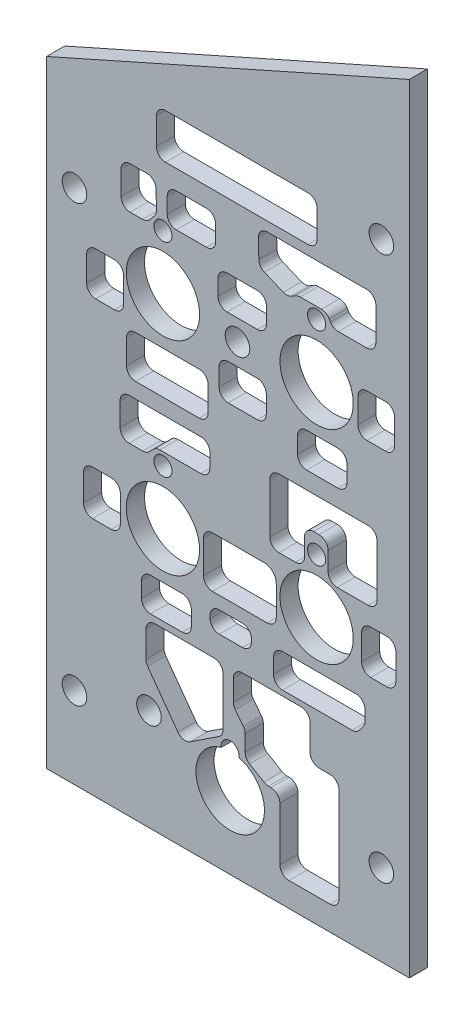
SolidWorks part; units mm, degrees
material "PET"
ref_plane "Front Plane" through (0, 0, 0) normal (0, 0, 1) x (1, 0, 0)
ref_plane "Top Plane" through (0, 0, 0) normal (0, 1, 0) x (1, 0, 0)
ref_plane "Right Plane" through (0, 0, 0) normal (1, 0, 0) x (0, 0, -1)
sketch "Sketch1" plane through (0, 0, 0) normal (0, 0, 1) x (1, 0, 0)
  line L4 (0, 107.95) -> (0, 0)
  line L5 (0, 0) -> (63.5, 0)
  line L6 (63.5, 0) -> (63.5, 136.2202)
  line L7 (63.5, 136.2202) -> (0, 107.95)
  line L8 (0, 107.95) -> (0, 0)
  line L9 (0, 0) -> (63.5, 0)
  line L10 (63.5, 0) -> (63.5, 136.2202)
  line L11 (63.5, 136.2202) -> (0, 107.95)
  dimension "D1" = 0
extrude "Boss-Extrude1" add sketch "Sketch1" against normal blind 3.175
hole_wizard "#6 Clearance Hole1" positions "Sketch4" profile "Sketch3" hole size "#6" standard "ANSI Inch" end condition through all
sketch "Sketch4" plane through (0, 0, 0) normal (0, 0, 1) x (1, 0, 0)
  point P0 (58.6105, 14.2875)
  point P3 (4.8895, 14.2875)
  point P6 (4.8895, 90.4875)
  point P9 (58.6105, 109.5375)
sketch "Sketch3" plane through (58.6105, 14.2875, 0) normal (1, 0, 0) x (0, -1, 0)
  line L0 (0, 0) -> (0, 3.175)
  line L1 (0, 3.175) -> (2.1526, 3.175)
  line L2 (2.1526, 3.175) -> (2.1526, 0)
  line L5 (2.1526, 0) -> (0, 0)
  line L11 (0, -6.35) -> (0, 107.95) construction
  dimension "Thru Hole Dia." = 4.3053
  dimension "Thru Hole Depth" = 3.175
sketch "Sketch8" plane through (0, 0, 0) normal (0, 0, 1) x (1, 0, 0)
  line L0 (0, 0) -> (63.5, 0) construction
  line L1 (20.3732, 91.7104) -> (20.3732, 82.1854) construction
  line L2 (20.3732, 56.073) -> (20.3732, 46.548) construction
  line L3 (47.2705, 46.548) -> (47.2705, 56.073) construction
  line L4 (32.1439, 18.7) -> (32.1439, 12.7) construction
  line L5 (81.6444, 34.0155) -> (81.6444, 24.4905) construction
  line L6 (47.2705, 82.1854) -> (47.2705, 91.7104) construction
  line L7 (0, 107.95) -> (0, 0) construction
  circle A1 centre (20.3732, 91.7104) radius 1.5875
  circle A2 centre (47.2705, 91.7104) radius 1.5875
  circle A3 centre (47.2705, 56.073) radius 1.5875
  circle A4 centre (32.1439, 12.7) radius 3.75
  circle A5 centre (20.3732, 56.073) radius 1.5875
  circle A6 centre (32.1439, 18.7) radius 1.5875
  circle A10 centre (47.2705, 46.548) radius 6.4135
  circle A12 centre (47.2705, 82.1854) radius 6.4135
  circle A15 centre (20.3732, 82.1854) radius 6.4135
  circle A17 centre (20.3732, 46.548) radius 6.4135
  circle A18 centre (81.6444, 34.0155) radius 1.651 construction
  circle A19 centre (81.6444, 24.4905) radius 6.4135 construction
  dimension "D2" = 26.8973
  dimension "D3" = 12.827
  dimension "D9" = 3.175
  dimension "D10" = 3.175
  dimension "D11" = 3.175
  dimension "D12" = 3.175
  dimension "D13" = 3.175
  dimension "D14" = 7.5
  dimension "D1" = 9.525
  dimension "D4" = 35.6374
  dimension "D5" = 33.848
  dimension "D6" = 15.1266
  dimension "D7" = 12.7
  dimension "D8" = 32.1439
  dimension "D15" = 6
extrude "Cut-Extrude1" cut sketch "Sketch8" against normal through all
hole_wizard "#6 Clearance Hole2" positions "Sketch9" profile "Sketch10" hole size "#6" standard "ANSI Inch" end condition through all
sketch "Sketch9" plane through (31.75, 0, 4.765) normal (0, 0, 1) x (1, 0, 0)
  point P0 (1.6763, 81.3834)
  point P2 (-13.8187, 17.7712)
sketch "Sketch10" plane through (33.4263, 81.3834, 4.765) normal (1, 0, 0) x (0, -1, 0)
  line L0 (0, 0) -> (0, 7.94)
  line L1 (0, 7.94) -> (2.1526, 7.94)
  line L2 (2.1526, 7.94) -> (2.1526, 0)
  line L3 (2.1526, 0) -> (0, 0)
  line L4 (0, -6.35) -> (0, 107.95) construction
  dimension "Thru Hole Dia." = 4.3053
  dimension "Thru Hole Depth" = 7.94
sketch "Sketch11" plane through (0, 0, 0) normal (0, 0, 1) x (1, 0, 0)
  line L36 (45.5237, 74.0554) -> (50.9898, 74.0554)
  line L37 (43.9362, 72.4679) -> (43.9362, 69.6013)
  line L38 (45.5237, 68.0138) -> (50.9898, 68.0138)
  line L39 (52.5773, 72.4679) -> (52.5773, 69.6013)
  line L41 (13.9834, 72.3188) -> (13.9834, 68.071)
  line L47 (28.2901, 72.3188) -> (28.2901, 68.071)
  line L120 (56.0781, 85.2958) -> (59.3407, 85.2958)
  line L121 (54.4906, 83.7083) -> (54.4906, 79.3729)
  line L122 (56.0781, 77.7854) -> (59.3407, 77.7854)
  line L123 (60.9282, 83.7083) -> (60.9282, 79.3729)
  line L124 (8.6064, 83.088) -> (11.8928, 83.088)
  line L125 (7.0189, 81.5005) -> (7.0189, 77.085)
  line L126 (8.6064, 75.4975) -> (11.8928, 75.4975)
  line L127 (13.4803, 81.5005) -> (13.4803, 77.085)
  line L132 (31.7883, 77.6009) -> (36.873, 77.6009)
  line L133 (30.2008, 76.0134) -> (30.2008, 72.9194)
  line L134 (31.7883, 71.3319) -> (36.873, 71.3319)
  line L135 (38.4605, 76.0134) -> (38.4605, 72.9194)
  line L140 (20.8125, 110.1622) -> (45.7836, 110.1622)
  line L141 (47.3711, 108.5747) -> (47.3711, 103.9202)
  line L142 (45.7836, 102.3327) -> (20.8125, 102.3327)
  line L143 (19.225, 103.9202) -> (19.225, 108.5747)
  line L144 (57.6403, 99.0765) -> (57.6403, 93.3678)
  line L145 (56.0528, 91.7803) -> (51.0669, 91.7803)
  line L146 (49.7101, 92.5437) -> (49.4755, 92.93)
  line L147 (48.1187, 93.6933) -> (44.3958, 93.6933)
  line L148 (43.5716, 93.4626) -> (42.8862, 93.0463)
  line L149 (41.4551, 92.9362) -> (38.1407, 94.3076)
  line L150 (37.1609, 95.7286) -> (37.0654, 99.0307)
  line L151 (38.6523, 100.664) -> (56.0528, 100.664)
  line L152 (13.0431, 97.4222) -> (13.0431, 93.2456)
  line L153 (14.6306, 91.6581) -> (16.8223, 91.6581)
  line L154 (18.0448, 92.2329) -> (18.8858, 93.2482)
  line L155 (19.2501, 94.3076) -> (19.1571, 97.4689)
  line L156 (17.5703, 99.0097) -> (14.6306, 99.0097)
  line L157 (21.1275, 97.349) -> (21.1275, 94.6082)
  line L158 (22.715, 93.0207) -> (28.002, 93.0207)
  line L159 (29.5895, 94.6082) -> (29.5895, 97.349)
  line L160 (28.002, 98.9365) -> (22.715, 98.9365)
  line L161 (30.0099, 89.3456) -> (30.0099, 86.6058)
  line L162 (31.5974, 85.0183) -> (36.9051, 85.0183)
  line L163 (38.4926, 86.6058) -> (38.4926, 89.3456)
  line L164 (36.9051, 90.9331) -> (31.5974, 90.9331)
  line L165 (15.5709, 73.9063) -> (26.7026, 73.9063)
  line L166 (15.5709, 66.4835) -> (26.7026, 66.4835)
  line L167 (39.0901, 54.653) -> (39.0901, 63.4087)
  line L168 (40.6776, 64.9962) -> (56.2883, 64.9962)
  line L169 (57.8758, 63.4087) -> (57.8758, 54.4828)
  line L170 (56.2883, 52.8953) -> (50.8752, 52.8953)
  line L171 (49.2877, 54.4828) -> (49.2877, 57.7132)
  line L172 (47.7002, 59.3007) -> (46.7435, 59.3007)
  line L173 (45.156, 57.7132) -> (45.156, 54.653)
  line L174 (43.5685, 53.0655) -> (40.6776, 53.0655)
  line L175 (55.758, 36.8172) -> (55.758, 35.0552)
  line L176 (34.2696, 35.4833) -> (30.227, 35.4833)
  line L177 (35.8571, 37.0708) -> (35.8571, 37.5884)
  line L178 (34.2696, 39.1759) -> (30.227, 39.1759)
  line L179 (28.6395, 37.0708) -> (28.6395, 37.5884)
  line L180 (55.4332, 34.0931) -> (54.7305, 33.1708)
  line L181 (53.4677, 32.5454) -> (41.3186, 32.5454)
  line L182 (39.7311, 34.1329) -> (39.7311, 36.8172)
  line L183 (41.3186, 38.4047) -> (54.1705, 38.4047)
  line L184 (25.1503, 16.6335) -> (30.1748, 19.9489)
  line L185 (30.8879, 21.2739) -> (30.8879, 29.8393)
  line L186 (29.3004, 31.4268) -> (18.9703, 31.4268)
  line L187 (17.3828, 29.8393) -> (17.3828, 25.2871)
  line L188 (17.6844, 24.3562) -> (22.9901, 17.0276)
  line L189 (32.6889, 30.0523) -> (32.6889, 26.4288)
  line L190 (33.0249, 25.4521) -> (34.4315, 23.6499)
  line L193 (40.8468, 15.1629) -> (40.8468, 5.8443)
  line L194 (42.4343, 4.2568) -> (49.6158, 4.2568)
  line L195 (51.2033, 5.8443) -> (51.2033, 22.3324)
  line L196 (49.6158, 23.9199) -> (47.7144, 23.9199)
  line L197 (46.1269, 25.5074) -> (46.1269, 30.0523)
  line L198 (44.5394, 31.6398) -> (34.2764, 31.6398)
  line L204 (38.1, 50.2578) -> (29.0541, 50.2578)
  line L205 (40.2083, 48.1495) -> (40.2083, 42.9683)
  line L206 (38.6208, 41.3808) -> (29.0541, 41.3808)
  line L207 (27.4666, 48.6703) -> (27.4666, 42.9683)
  line L210 (12.8755, 62.2158) -> (12.8755, 58.1379)
  line L211 (11.3334, 41.9242) -> (8.0566, 41.9242)
  line L212 (12.9209, 43.5117) -> (12.9209, 48.1495)
  line L213 (11.3334, 49.737) -> (8.0566, 49.737)
  line L214 (6.4691, 43.5117) -> (6.4691, 48.1495)
  line L215 (14.463, 56.5504) -> (16.8417, 56.5504)
  line L216 (17.9642, 57.0153) -> (18.708, 57.7591)
  line L217 (19.8305, 58.2241) -> (27.0058, 58.2241)
  line L218 (28.5933, 59.8116) -> (28.5933, 62.2158)
  line L219 (27.0058, 63.8033) -> (14.463, 63.8033)
  line L221 (18.2021, 38.4047) -> (23.7519, 38.4047)
  line L222 (16.6146, 36.8172) -> (16.6146, 34.1329)
  line L223 (18.2021, 32.5454) -> (23.7519, 32.5454)
  line L224 (25.3394, 36.8172) -> (25.3394, 34.1329)
  line L225 (56.7376, 49.8291) -> (59.5564, 49.8291)
  line L226 (55.1501, 48.2416) -> (55.1501, 43.7598)
  line L227 (56.7376, 42.1723) -> (59.5564, 42.1723)
  line L228 (61.1439, 48.2416) -> (61.1439, 43.7598)
  line L230 (34.7676, 22.6732) -> (34.7676, 19.8429)
  line L231 (35.535, 18.4836) -> (38.0298, 16.9786)
  line L232 (38.8498, 16.7504) -> (39.2593, 16.7504)
  circle A0 centre (32.1439, 12.7) radius 6
  arc A1 (20.8125, 102.3327) -> (19.225, 103.9202) centre (20.8125, 103.9202) cw
  arc A2 (47.3711, 103.9202) -> (45.7836, 102.3327) centre (45.7836, 103.9202) cw
  arc A3 (45.7836, 110.1622) -> (47.3711, 108.5747) centre (45.7836, 108.5747) cw
  arc A4 (20.8125, 110.1622) -> (19.225, 108.5747) centre (20.8125, 108.5747) ccw
  arc A9 (36.873, 77.6009) -> (38.4605, 76.0134) centre (36.873, 76.0134) cw
  arc A10 (30.2008, 72.9194) -> (31.7883, 71.3319) centre (31.7883, 72.9194) ccw
  arc A11 (36.873, 71.3319) -> (38.4605, 72.9194) centre (36.873, 72.9194) ccw
  arc A12 (31.7883, 77.6009) -> (30.2008, 76.0134) centre (31.7883, 76.0134) ccw
  arc A13 (11.8928, 83.088) -> (13.4803, 81.5005) centre (11.8928, 81.5005) cw
  arc A14 (7.0189, 77.085) -> (8.6064, 75.4975) centre (8.6064, 77.085) ccw
  arc A15 (11.8928, 75.4975) -> (13.4803, 77.085) centre (11.8928, 77.085) ccw
  arc A16 (8.6064, 83.088) -> (7.0189, 81.5005) centre (8.6064, 81.5005) ccw
  arc A17 (59.3407, 85.2958) -> (60.9282, 83.7083) centre (59.3407, 83.7083) cw
  arc A18 (54.4906, 79.3729) -> (56.0781, 77.7854) centre (56.0781, 79.3729) ccw
  arc A19 (59.3407, 77.7854) -> (60.9282, 79.3729) centre (59.3407, 79.3729) ccw
  arc A20 (56.0781, 85.2958) -> (54.4906, 83.7083) centre (56.0781, 83.7083) ccw
  arc A29 (46.1269, 30.0523) -> (44.5394, 31.6398) centre (44.5394, 30.0523) ccw
  arc A30 (47.7144, 23.9199) -> (46.1269, 25.5074) centre (47.7144, 25.5074) cw
  arc A31 (49.6158, 4.2568) -> (51.2033, 5.8443) centre (49.6158, 5.8443) ccw
  arc A32 (51.2033, 22.3324) -> (49.6158, 23.9199) centre (49.6158, 22.3324) ccw
  arc A33 (40.8468, 5.8443) -> (42.4343, 4.2568) centre (42.4343, 5.8443) ccw
  arc A36 (34.4315, 23.6499) -> (34.7676, 22.6732) centre (33.1801, 22.6732) cw
  arc A37 (32.6889, 26.4288) -> (33.0249, 25.4521) centre (34.2764, 26.4288) ccw
  arc A38 (32.6889, 30.0523) -> (34.2764, 31.6398) centre (34.2764, 30.0523) cw
  arc A39 (17.3828, 25.2871) -> (17.6844, 24.3562) centre (18.9703, 25.2871) ccw
  arc A40 (18.9703, 31.4268) -> (17.3828, 29.8393) centre (18.9703, 29.8393) ccw
  arc A41 (30.8879, 29.8393) -> (29.3004, 31.4268) centre (29.3004, 29.8393) ccw
  arc A42 (29.0541, 50.2578) -> (27.4666, 48.6703) centre (29.0541, 48.6703) ccw
  arc A43 (40.2083, 42.9683) -> (38.6208, 41.3808) centre (38.6208, 42.9683) cw
  arc A44 (29.0541, 41.3808) -> (27.4666, 42.9683) centre (29.0541, 42.9683) cw
  arc A46 (38.1, 50.2578) -> (40.2083, 48.1495) centre (38.1, 48.1495) cw
  arc A49 (26.7026, 73.9063) -> (28.2901, 72.3188) centre (26.7026, 72.3188) cw
  arc A50 (30.1748, 19.9489) -> (30.8879, 21.2739) centre (29.3004, 21.2739) ccw
  arc A51 (26.7026, 66.4835) -> (28.2901, 68.071) centre (26.7026, 68.071) ccw
  arc A52 (25.1503, 16.6335) -> (22.9901, 17.0276) centre (24.276, 17.9585) cw
  arc A53 (39.7311, 36.8172) -> (41.3186, 38.4047) centre (41.3186, 36.8172) cw
  arc A54 (13.9834, 68.071) -> (15.5709, 66.4835) centre (15.5709, 68.071) ccw
  arc A55 (54.7305, 33.1708) -> (53.4677, 32.5454) centre (53.4677, 34.1329) cw
  arc A56 (15.5709, 73.9063) -> (13.9834, 72.3188) centre (15.5709, 72.3188) ccw
  arc A57 (50.9898, 74.0554) -> (52.5773, 72.4679) centre (50.9898, 72.4679) cw
  arc A58 (43.9362, 69.6013) -> (45.5237, 68.0138) centre (45.5237, 69.6013) ccw
  arc A59 (50.9898, 68.0138) -> (52.5773, 69.6013) centre (50.9898, 69.6013) ccw
  arc A60 (45.5237, 74.0554) -> (43.9362, 72.4679) centre (45.5237, 72.4679) ccw
  arc A61 (41.3186, 32.5454) -> (39.7311, 34.1329) centre (41.3186, 34.1329) cw
  arc A62 (55.758, 35.0552) -> (55.4332, 34.0931) centre (54.1705, 35.0552) cw
  arc A63 (55.758, 36.8172) -> (54.1705, 38.4047) centre (54.1705, 36.8172) ccw
  arc A64 (30.227, 35.4833) -> (28.6395, 37.0708) centre (30.227, 37.0708) cw
  arc A65 (35.8571, 37.5884) -> (34.2696, 39.1759) centre (34.2696, 37.5884) ccw
  arc A66 (40.6776, 53.0655) -> (39.0901, 54.653) centre (40.6776, 54.653) cw
  arc A67 (45.156, 54.653) -> (43.5685, 53.0655) centre (43.5685, 54.653) cw
  arc A68 (30.227, 39.1759) -> (28.6395, 37.5884) centre (30.227, 37.5884) ccw
  arc A69 (46.7435, 59.3007) -> (45.156, 57.7132) centre (46.7435, 57.7132) ccw
  arc A70 (50.8752, 52.8953) -> (49.2877, 54.4828) centre (50.8752, 54.4828) cw
  arc A71 (49.2877, 57.7132) -> (47.7002, 59.3007) centre (47.7002, 57.7132) ccw
  arc A72 (57.8758, 54.4828) -> (56.2883, 52.8953) centre (56.2883, 54.4828) cw
  arc A73 (56.2883, 64.9962) -> (57.8758, 63.4087) centre (56.2883, 63.4087) cw
  arc A74 (39.0901, 63.4087) -> (40.6776, 64.9962) centre (40.6776, 63.4087) cw
  arc A75 (34.2696, 35.4833) -> (35.8571, 37.0708) centre (34.2696, 37.0708) ccw
  arc A76 (38.4926, 89.3456) -> (36.9051, 90.9331) centre (36.9051, 89.3456) ccw
  arc A77 (36.9051, 85.0183) -> (38.4926, 86.6058) centre (36.9051, 86.6058) ccw
  arc A78 (30.0099, 86.6058) -> (31.5974, 85.0183) centre (31.5974, 86.6058) ccw
  arc A79 (30.0099, 89.3456) -> (31.5974, 90.9331) centre (31.5974, 89.3456) cw
  arc A80 (29.5895, 97.349) -> (28.002, 98.9365) centre (28.002, 97.349) ccw
  arc A81 (28.002, 93.0207) -> (29.5895, 94.6082) centre (28.002, 94.6082) ccw
  arc A82 (21.1275, 94.6082) -> (22.715, 93.0207) centre (22.715, 94.6082) ccw
  arc A83 (21.1275, 97.349) -> (22.715, 98.9365) centre (22.715, 97.349) cw
  arc A84 (19.1571, 97.4689) -> (17.5703, 99.0097) centre (17.5703, 97.4222) ccw
  arc A85 (18.8858, 93.2482) -> (19.2501, 94.3076) centre (17.6633, 94.2609) ccw
  arc A86 (16.8223, 91.6581) -> (18.0448, 92.2329) centre (16.8223, 93.2456) ccw
  arc A87 (13.0431, 93.2456) -> (14.6306, 91.6581) centre (14.6306, 93.2456) ccw
  arc A88 (37.0654, 99.0307) -> (38.6523, 100.664) centre (38.6523, 99.0765) cw
  arc A89 (13.0431, 97.4222) -> (14.6306, 99.0097) centre (14.6306, 97.4222) cw
  arc A90 (38.1407, 94.3076) -> (37.1609, 95.7286) centre (38.7477, 95.7745) cw
  arc A91 (42.8862, 93.0463) -> (41.4551, 92.9362) centre (42.062, 94.4031) cw
  arc A92 (44.3958, 93.6933) -> (43.5716, 93.4626) centre (44.3958, 92.1058) ccw
  arc A93 (49.4755, 92.93) -> (48.1187, 93.6933) centre (48.1187, 92.1058) ccw
  arc A94 (51.0669, 91.7803) -> (49.7101, 92.5437) centre (51.0669, 93.3678) cw
  arc A95 (57.6403, 93.3678) -> (56.0528, 91.7803) centre (56.0528, 93.3678) cw
  arc A96 (57.6403, 99.0765) -> (56.0528, 100.664) centre (56.0528, 99.0765) ccw
  arc A97 (8.0566, 41.9242) -> (6.4691, 43.5117) centre (8.0566, 43.5117) cw
  arc A98 (12.9209, 48.1495) -> (11.3334, 49.737) centre (11.3334, 48.1495) ccw
  arc A99 (8.0566, 49.737) -> (6.4691, 48.1495) centre (8.0566, 48.1495) ccw
  arc A100 (11.3334, 41.9242) -> (12.9209, 43.5117) centre (11.3334, 43.5117) ccw
  arc A101 (28.5933, 62.2158) -> (27.0058, 63.8033) centre (27.0058, 62.2158) ccw
  arc A102 (27.0058, 58.2241) -> (28.5933, 59.8116) centre (27.0058, 59.8116) ccw
  arc A103 (16.8417, 56.5504) -> (17.9642, 57.0153) centre (16.8417, 58.1379) ccw
  arc A104 (18.708, 57.7591) -> (19.8305, 58.2241) centre (19.8305, 56.6366) cw
  arc A105 (12.8755, 58.1379) -> (14.463, 56.5504) centre (14.463, 58.1379) ccw
  arc A106 (12.8755, 62.2158) -> (14.463, 63.8033) centre (14.463, 62.2158) cw
  arc A107 (23.7519, 38.4047) -> (25.3394, 36.8172) centre (23.7519, 36.8172) cw
  arc A108 (16.6146, 34.1329) -> (18.2021, 32.5454) centre (18.2021, 34.1329) ccw
  arc A109 (23.7519, 32.5454) -> (25.3394, 34.1329) centre (23.7519, 34.1329) ccw
  arc A110 (18.2021, 38.4047) -> (16.6146, 36.8172) centre (18.2021, 36.8172) ccw
  arc A111 (59.5564, 49.8291) -> (61.1439, 48.2416) centre (59.5564, 48.2416) cw
  arc A112 (55.1501, 43.7598) -> (56.7376, 42.1723) centre (56.7376, 43.7598) ccw
  arc A113 (59.5564, 42.1723) -> (61.1439, 43.7598) centre (59.5564, 43.7598) ccw
  arc A114 (56.7376, 49.8291) -> (55.1501, 48.2416) centre (56.7376, 48.2416) ccw
  arc A115 (34.7676, 19.8429) -> (35.535, 18.4836) centre (36.3551, 19.8429) ccw
  arc A116 (38.0298, 16.9786) -> (38.8498, 16.7504) centre (38.8498, 18.3379) ccw
  arc A117 (39.2593, 16.7504) -> (40.8468, 15.1629) centre (39.2593, 15.1629) cw
  point P171 (0, 0)
  dimension "D1" = 1.5875
  dimension "D2" = 1.5875
  dimension "D3" = 1.5875
  dimension "D4" = 1.5875
  dimension "D5" = 1.5875
  dimension "D6" = 1.5875
extrude "Cut-Extrude2" cut sketch "Sketch11" against normal through all
